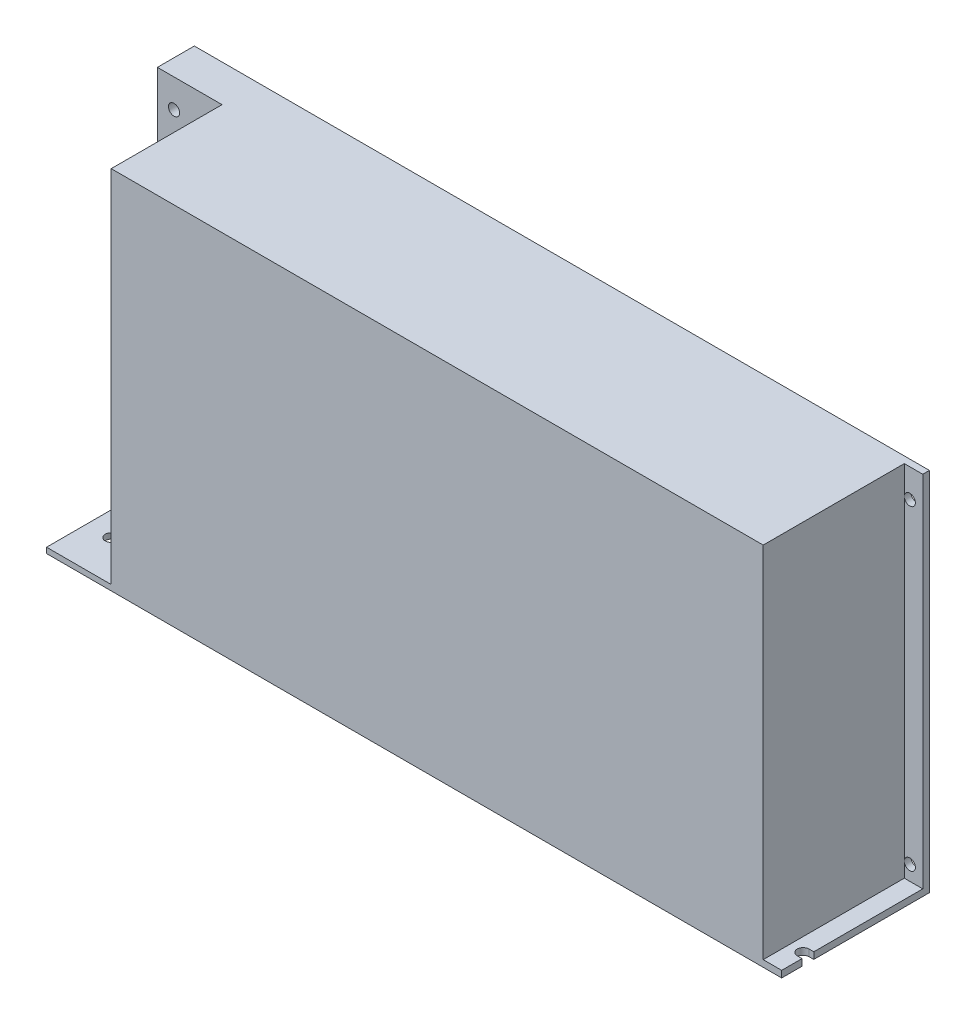
SolidWorks part; units mm, degrees
ref_plane "前视基准面" through (0, 0, 0) normal (0, 0, 1) x (1, 0, 0)
ref_plane "上视基准面" through (0, 0, 0) normal (0, 1, 0) x (1, 0, 0)
ref_plane "右视基准面" through (0, 0, 0) normal (1, 0, 0) x (0, 0, -1)
sketch "草图1" plane through (0, 0, 0) normal (0, 0, 1) x (1, 0, 0)
  line L0 (-145.1274, 0) -> (129.4602, 0) construction
  line L1 (-99.5, 49.5) -> (99.5, 49.5)
  line L2 (-99.5, 49.5) -> (-99.5, -49.5)
  line L3 (-99.5, -49.5) -> (99.5, -49.5)
  line L4 (99.5, 49.5) -> (99.5, -49.5)
  line L5 (0, 68.6007) -> (0, -70.3881) construction
  dimension "D1" = 99
  dimension "D2" = 199
extrude "拉伸1" add sketch "草图1" along normal blind 40
sketch "草图3" plane through (0, 0, 40) normal (0, 0, 1) x (1, 0, 0)
  line L1 (-99.5, -49.5) -> (99.5, -49.5) construction
  line L2 (-99.5, 49.5) -> (-82, 49.5)
  line L3 (-99.5, 49.5) -> (-99.5, -48)
  line L4 (-99.5, -48) -> (-82, -48)
  line L6 (-82, 49.5) -> (-82, -48)
  dimension "D1" = 17.5
  dimension "D2" = 1.5
extrude "切除-拉伸2" cut sketch "草图3" against normal offset from surface (30 mm away) 10 up to face at (0, 0, 0)
sketch "草图6" plane through (0, 49.5, 0) normal (0, 1, 0) x (-1, 0, 0)
  line L0 (-99.5, 0) -> (99.5, 0) construction
  line L1 (-99.5, 40) -> (-94.5, 40)
  line L2 (-99.5, 40) -> (-99.5, 1.8)
  line L3 (-99.5, 1.8) -> (-94.5, 1.8)
  line L4 (-94.5, 40) -> (-94.5, 1.8)
  dimension "D1" = 1.8
  dimension "D2" = 5
extrude "切除-拉伸5" cut sketch "草图6" against normal offset from surface (97.2 mm away) 1.8 up to face at (0, -49.5, 20)
sketch "草图7" plane through (0, 0, 10) normal (0, 0, 1) x (1, 0, 0)
  line L0 (-99.5, 49.5) -> (-99.5, -48) construction
  line L1 (-82, -48) -> (-99.5, -48)
  line L2 (-82, -48) -> (-82, -39)
  line L3 (-82, -39) -> (-99.5, -39)
  line L4 (-99.5, -48) -> (-99.5, -39)
  line L6 (94.5, 49.5) -> (-82, 49.5) construction
  dimension "D1" = 88.5
extrude "切除-拉伸6" cut sketch "草图7" against normal offset from surface (8.2 mm away) 1.8 up to face at (0, 0, 0)
sketch "草图2" plane through (0, 0, 0) normal (0, 0, 1) x (1, 0, 0)
  line L0 (99.5, -47.7) -> (99.5, 49.5) construction
  line L2 (-41.5, -45.7596) -> (-41.5, 72.1566) construction
  line L3 (-80.4338, -40.2) -> (88.2308, -40.2) construction
  line L4 (78.5, -41.7166) -> (78.5, 56.9614) construction
  line L5 (88.2308, 39.8) -> (-80.4338, 39.8) construction
  line L6 (-99.5, -49.5) -> (99.5, -49.5) construction
  circle A0 centre (-41.5, 39.8) radius 2
  circle A1 centre (78.5, 39.8) radius 2
  circle A2 centre (-41.5, -40.2) radius 2
  circle A3 centre (78.5, -40.2) radius 2
  dimension "D1" = 21
  dimension "D2" = 120
  dimension "D3" = 80
  dimension "D4" = 4
  dimension "D5" = 4
  dimension "D6" = 4
  dimension "D7" = 4
  dimension "D9" = 9.3
extrude "切除-拉伸1" cut sketch "草图2" along normal blind 10
sketch "草图4" plane through (0, -49.5, 0) normal (0, -1, 0) x (1, 0, 0)
  line L0 (94.9806, 12.5) -> (-156.73, 12.5) construction
  line L1 (-99.5, 40) -> (99.5, 40) construction
  line L2 (-99.5, 0) -> (99.5, 0) construction
  line L3 (-79.5, -14.188) -> (-79.5, 56.6156) construction
  line L4 (77.5, -14.188) -> (77.5, 66.81) construction
  line L5 (99.5, 40) -> (99.5, 0) construction
  line L7 (90.0302, 30.5) -> (-119.4663, 30.5) construction
  circle A0 centre (-79.5, 20) radius 1.5
  circle A1 centre (77.5, 12.5) radius 1.5
  circle A2 centre (77.5, 30.5) radius 1.5
  dimension "D3" = 20
  dimension "D4" = 3
  dimension "D5" = 22
  dimension "D6" = 3
  dimension "D8" = 3
  dimension "D1" = 9.5
  dimension "D2" = 157
  dimension "D7" = 18
extrude "切除-拉伸3" cut sketch "草图4" against normal blind 10
sketch "草图5" plane through (0, -49.5, 0) normal (0, -1, 0) x (1, 0, 0)
  line L0 (-126.2446, 29) -> (142.4148, 29) construction
  line L1 (-93, 38.2624) -> (-93, 28.9624) construction
  line L2 (99.5, 34.5) -> (99.5, 31.3)
  line L3 (-99.5, 0) -> (99.5, 0) construction
  line L4 (-99.5, 40) -> (-99.5, 0) construction
  line L6 (99.5, 34.5) -> (98.2, 34.5)
  line L7 (99.5, 40) -> (99.5, 0) construction
  line L8 (99.5, 31.3) -> (98.2, 31.3)
  line L9 (98.2, 41.8241) -> (98.2, 47.3634) construction
  line L10 (109.3024, 32.9) -> (74.1624, 32.9) construction
  line L11 (-99.5, 40) -> (99.5, 40) construction
  circle A0 centre (-93, 29) radius 1.6
  arc A1 (98.2, 34.5) -> (98.2, 31.3) centre (98.2, 32.9) ccw
  dimension "D3" = 3.2
  dimension "D1" = 29
  dimension "D2" = 6.5
  dimension "D4" = 3.2
  dimension "D5" = 1.3
  dimension "D6" = 5.5
extrude "切除-拉伸4" cut sketch "草图5" against normal blind 10
sketch "草图8" plane through (0, 0, 0) normal (0, 0, -1) x (-1, 0, 0)
  line L0 (-122.4127, -0.95) -> (127.5607, -0.95) construction
  line L1 (-0.5, 73.4212) -> (-0.5, -72.5444) construction
  line L2 (-105.8702, 41.8) -> (105.7583, 41.8) construction
  line L3 (-96, 56.4915) -> (-96, -63.206) construction
  line L4 (-105.8702, -43.7) -> (105.7583, -43.7) construction
  line L5 (95, 56.4915) -> (95, -63.206) construction
  line L6 (99.5, -49.5) -> (-99.5, -49.5) construction
  line L7 (99.5, 49.5) -> (99.5, -49.5) construction
  circle A0 centre (-96, 41.8) radius 1.5
  circle A1 centre (-96, -43.7) radius 1.5
  circle A2 centre (95, -43.7) radius 1.5
  circle A3 centre (95, 41.8) radius 1.5
  dimension "D3" = 85.5
  dimension "D4" = 5.8
  dimension "D1" = 3
  dimension "D2" = 191
  dimension "D5" = 4.5
extrude "切除-拉伸7" cut sketch "草图8" against normal through all
